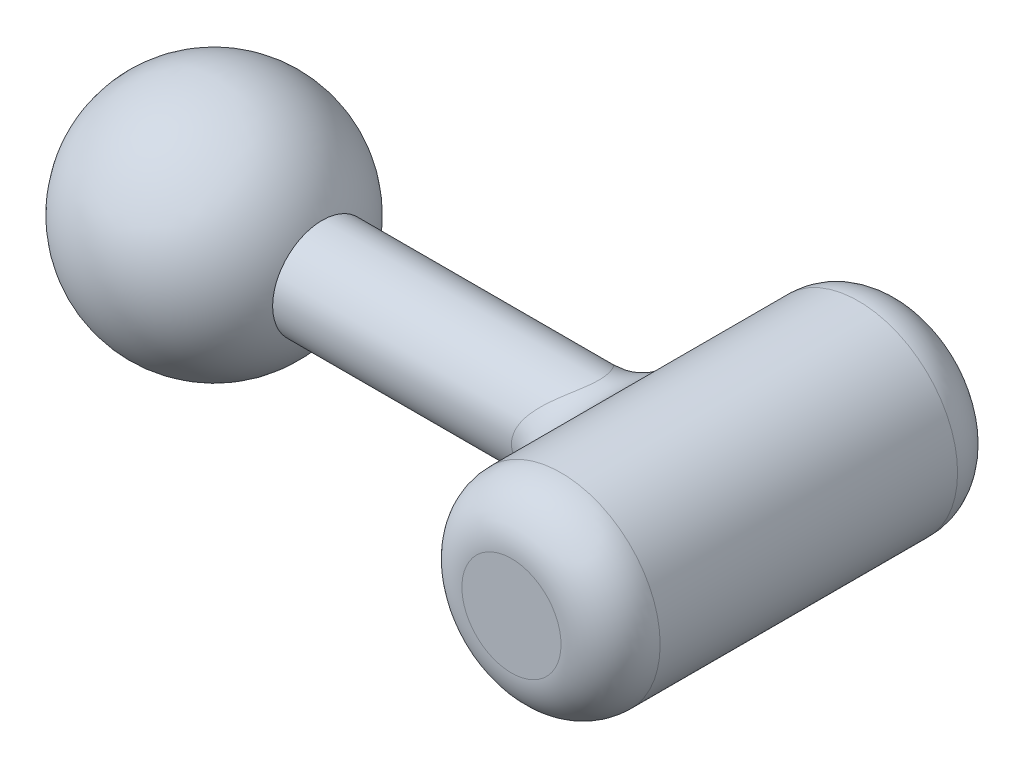
SolidWorks part; units mm, degrees
ref_plane "前视基准面" through (0, 0, 0) normal (0, 0, 1) x (1, 0, 0)
ref_plane "上视基准面" through (0, 0, 0) normal (0, 1, 0) x (1, 0, 0)
ref_plane "右视基准面" through (0, 0, 0) normal (1, 0, 0) x (0, 0, -1)
sketch "草图1" plane through (0, 0, 0) normal (0, 0, 1) x (1, 0, 0)
  line L0 (0, 0) -> (5, 0) construction
  line L1 (1.0909, 0.5) -> (5, 0.5)
  line L3 (5, 0.5) -> (5, 0)
  line L5 (0, 1) -> (15, -1) construction
  line L6 (5, 0.5) -> (19.8494, -2.4699) construction
  line L7 (-0.6, 0) -> (-1.2, 0)
  line L8 (3.2668, 0) -> (4, 0)
  line L9 (4, 0) -> (5, 0)
  line L10 (0.6, 0) -> (3.2668, 0)
  arc A3 (1.0909, 0.5) -> (-1.2, 0) centre (0, 0) ccw
  arc A4 (0.6, 0) -> (-0.6, 0) centre (0, 0) ccw
  point P6 (7.5, 0)
  dimension "D1" = 0.6
  dimension "D3" = 0.5
  dimension "D4" = 1.2
  dimension "D2" = 5
revolve "旋转2" add sketch "草图1" angle 360 about L0
sketch "草图2" plane through (0, 0, 0) normal (0, 0, 1) x (1, 0, 0)
  circle A0 centre (5, 0) radius 1
  point P0 (5, 0)
  dimension "D2" = 2
  dimension "D1" = 5
extrude "凸台-拉伸1" add sketch "草图2" along normal mid plane 4
fillet "圆角1" radius 0.5 3 edges at (4.0013, 0.0505, -0.4974) (6, 0, -2) (6, 0, 2)
